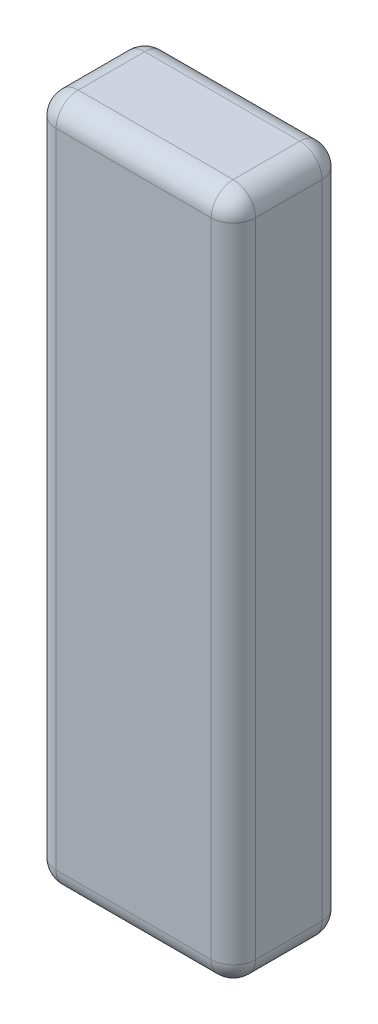
SolidWorks part; units mm, degrees
ref_plane "Front Plane" through (0, 0, 0) normal (0, 0, 1) x (1, 0, 0)
ref_plane "Top Plane" through (0, 0, 0) normal (0, 1, 0) x (1, 0, 0)
ref_plane "Right Plane" through (0, 0, 0) normal (1, 0, 0) x (0, 0, -1)
sketch "Sketch1" plane through (0, 0, 0) normal (0, 1, 0) x (1, 0, 0)
  line L1 (-9, -5) -> (9, -5)
  line L2 (-9, -5) -> (-9, 5)
  line L3 (-9, 5) -> (9, 5)
  line L4 (9, -5) -> (9, 5)
  line L5 (-9, -5) -> (9, 5) construction
  line L6 (-9, 5) -> (9, -5) construction
  point P0 (0, 0)
  dimension "D1" = 10
  dimension "D2" = 18
extrude "Boss-Extrude1" add sketch "Sketch1" along normal blind 62
fillet "Fillet1" radius 2 12 edges at (-9, 62, 0) (0, 62, -5) (9, 62, 0) (0, 62, 5) (0, 0, 5) (9, 0, 0) (-9, 0, 0) (0, 0, -5) (-9, 31, 5) (-9, 31, -5) (9, 31, -5) (9, 31, 5)
